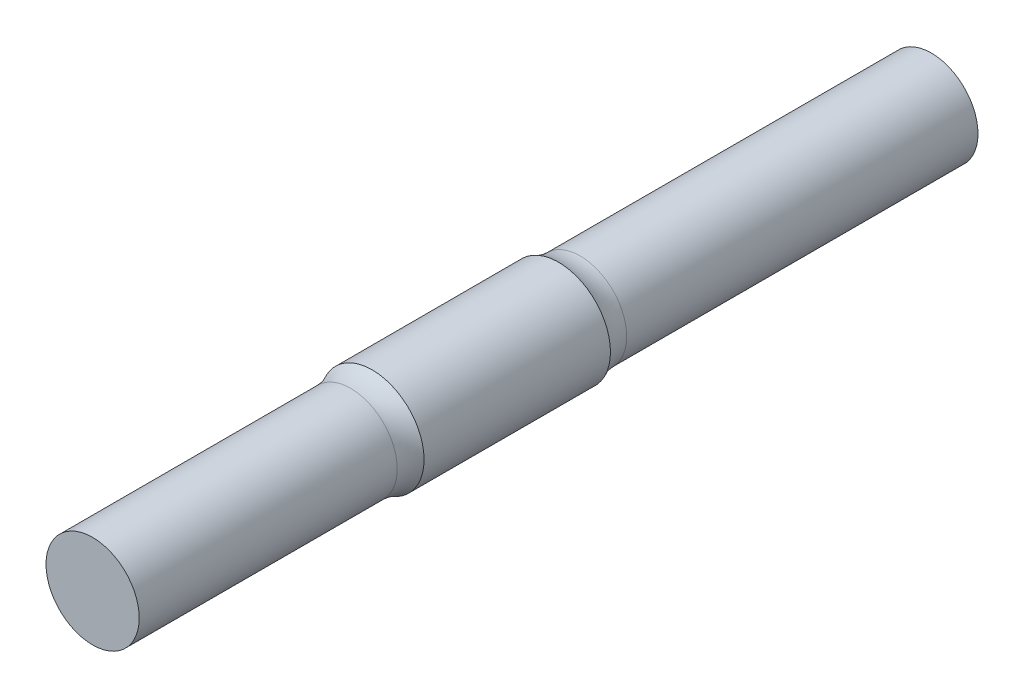
SolidWorks part; units mm, degrees
ref_plane "Front Plane" through (0, 0, 0) normal (0, 0, 1) x (1, 0, 0)
ref_plane "Top Plane" through (0, 0, 0) normal (0, 1, 0) x (1, 0, 0)
ref_plane "Right Plane" through (0, 0, 0) normal (1, 0, 0) x (0, 0, -1)
sketch "Sketch1" plane through (0, 0, 0) normal (0, 0, 1) x (1, 0, 0)
  circle A0 centre (0, 0) radius 5.565
  dimension "D1" = 11.13
extrude "Boss-Extrude1" add sketch "Sketch1" along normal mid plane 20
sketch "Sketch2" plane through (0, 0, 10) normal (0, 0, 1) x (1, 0, 0)
  circle A0 centre (0, 0) radius 5
extrude "Boss-Extrude2" add sketch "Sketch2" along normal blind 30
sketch "Sketch3" plane through (0, 0, -10) normal (0, 0, -1) x (-1, 0, 0)
  circle A0 centre (0, 0) radius 5
extrude "Boss-Extrude3" add sketch "Sketch3" along normal blind 40
fillet "Fillet2" radius 5 2 edges at (5, 0, 10) (-5, 0, -10)
